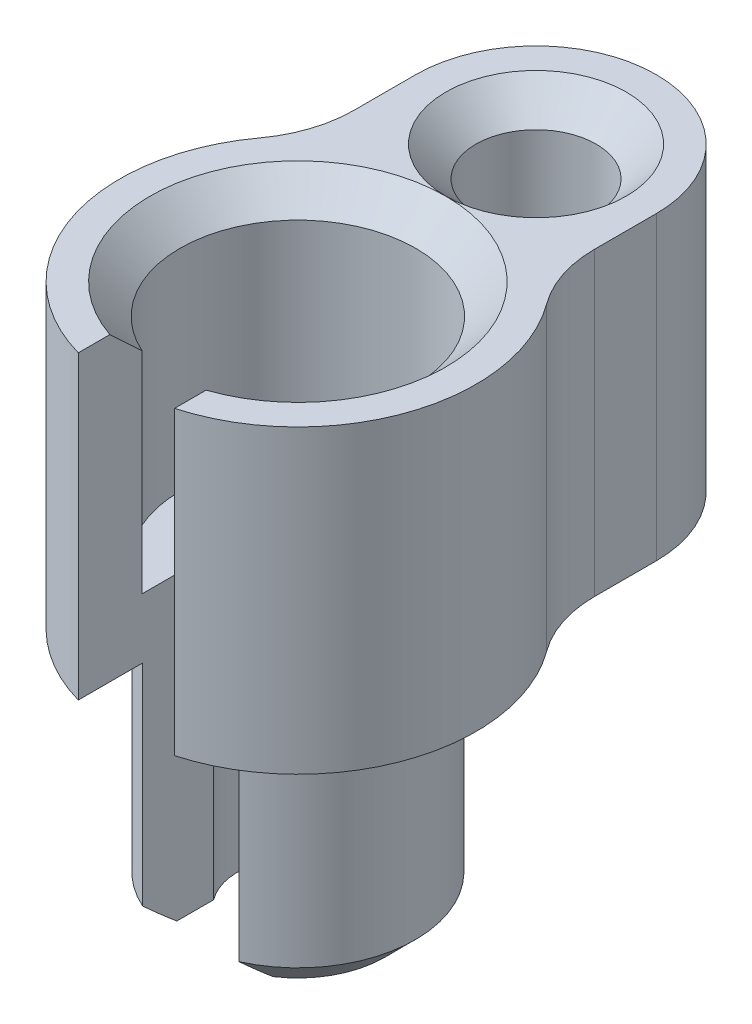
SolidWorks part; units mm, degrees
ref_plane "Front Plane" through (0, 0, 0) normal (0, 0, 1) x (1, 0, 0)
ref_plane "Top Plane" through (0, 0, 0) normal (0, 1, 0) x (1, 0, 0)
ref_plane "Right Plane" through (0, 0, 0) normal (1, 0, 0) x (0, 0, -1)
sketch "Sketch1" plane through (0, 0, 0) normal (0, 0, 1) x (1, 0, 0)
  line L0 (1.5875, 0) -> (1.5875, 14.2875)
  line L1 (1.5875, 14.2875) -> (4.699, 14.2875)
  line L2 (4.699, 14.2875) -> (4.699, 6.35)
  line L3 (4.699, 6.35) -> (3.0988, 6.35)
  line L4 (3.0988, 6.35) -> (3.0988, 0)
  line L5 (3.0988, 0) -> (1.5875, 0)
  line L6 (0, 0.1209) -> (0, -8357.9461) construction
  line L7 (1.5875, 7.9375) -> (3.1115, 7.9375)
  line L8 (3.1115, 7.9375) -> (3.1115, 14.2875)
  point P11 (4.699, 10.3187)
  dimension "D1" = 6.1976
  dimension "D2" = 3.175
  dimension "D3" = 6.35
  dimension "D4" = 1.5875
  dimension "D5" = 1.5875
  dimension "D6" = 6.223
  dimension "D7" = 6.35
revolve "Revolve1" add sketch "Sketch1" angle 360 about L6 region at (3.1434, 7.2218, 0)
sketch "Sketch2" plane through (0, 0, 0) normal (0, 0, 1) x (1, 0, 0)
  line L0 (4.699, 14.2875) -> (-4.699, 14.2875) construction
  line L1 (-1.27, 0) -> (1.27, 0)
  line L2 (-1.27, 0) -> (-1.27, 14.2875)
  line L3 (-1.27, 14.2875) -> (1.27, 14.2875)
  line L4 (1.27, 0) -> (1.27, 14.2875)
  line L5 (-1.27, 0) -> (1.27, 14.2875) construction
  line L6 (-1.27, 14.2875) -> (1.27, 0) construction
  point P0 (0, 7.1437)
  point P7 (0, 0)
  point P9 (0, 0)
  point P11 (0, 0)
  dimension "D1" = 2.54
extrude "Cut-Extrude1" cut sketch "Sketch2" along normal through all
sketch "Sketch3" plane through (0, 0, 0) normal (1, 0, 0) x (0, 0, -1)
  line L0 (4.699, 14.2875) -> (9.4615, 14.2875)
  line L1 (9.4615, 14.2875) -> (9.4615, 6.35)
  line L2 (9.4615, 6.35) -> (4.699, 6.35)
  line L3 (-4.5241, 6.35) -> (4.699, 6.35) construction
  line L4 (4.699, 6.35) -> (4.699, 14.2875)
  line L5 (6.2865, 12.7) -> (4.699, 14.2875) construction
  line L6 (7.874, 7.9375) -> (6.2865, 7.9375)
  line L7 (7.874, 7.9375) -> (7.874, 12.7)
  line L8 (7.874, 12.7) -> (6.2865, 12.7)
  line L9 (6.2865, 7.9375) -> (6.2865, 12.7)
  line L10 (7.874, 7.9375) -> (6.2865, 12.7) construction
  line L11 (7.874, 12.7) -> (6.2865, 7.9375) construction
  line L12 (9.4615, 14.2875) -> (7.874, 12.7) construction
  line L13 (9.4615, 6.35) -> (7.874, 7.9375) construction
  line L14 (6.2865, 7.9375) -> (4.699, 6.35) construction
  line L15 (6.2865, 12.7) -> (6.2865, 14.2875) construction
  line L16 (6.2865, 12.7) -> (4.699, 12.7) construction
  line L17 (4.699, 14.2875) -> (3.1115, 14.2875)
  line L19 (3.1115, 14.2875) -> (3.1115, 6.35)
  line L20 (3.1115, 6.35) -> (4.699, 6.35)
  point P3 (7.0803, 10.3187)
  point P12 (0, 0)
  point P19 (0, 0)
  dimension "D1" = 1.5875
  dimension "D2" = 1.5875
extrude "Boss-Extrude2" add sketch "Sketch3" along normal mid plane 6.35 contours L19 L20 L4 L17 | L4 L2 L1 L0 L6 L9 L8 L7 | L9 L6 L7 L8 region at (0, 14.1949, -7.0803) region at (0, 10.3187, -3.9053) region at (0, 10.3187, -7.0803)
sketch "Sketch4" plane through (0, 14.2875, 0) normal (0, 1, 0) x (1, 0, 0)
  line L1 (0, 6.2865) -> (0, 9.4615) construction
  line L2 (3.175, 9.4615) -> (-3.175, 9.4615) construction
  line L3 (0, 6.2865) -> (3.175, 6.2865) construction
  line L4 (3.175, 9.4615) -> (3.175, 3.4641) construction
  circle A0 centre (0, 6.2865) radius 1.5875
  circle A1 centre (0, 0) radius 4.699
  arc A2 (1.27, -4.5241) -> (3.175, 3.4641) centre (0, 0) ccw construction
  point P5 (0, 6.8194)
  dimension "D1" = 3.175
extrude "Cut-Extrude2" cut sketch "Sketch4" against normal through all contours A0 region at (0, 14.2875, -6.2865)
chamfer "Chamfer2" distance 0.7937 angle 45 4 edges at (0, 0, -3.0988) (0, 14.2875, -3.1115) (1.5875, 6.35, -6.2865) (-1.5875, 14.2875, -6.2865)
fillet "Fillet3" radius 3.175 4 edges at (-3.175, 10.3187, -3.4641) (3.175, 10.3187, -3.4641) (3.175, 10.3187, -9.4615) (-3.175, 10.3187, -9.4615)
